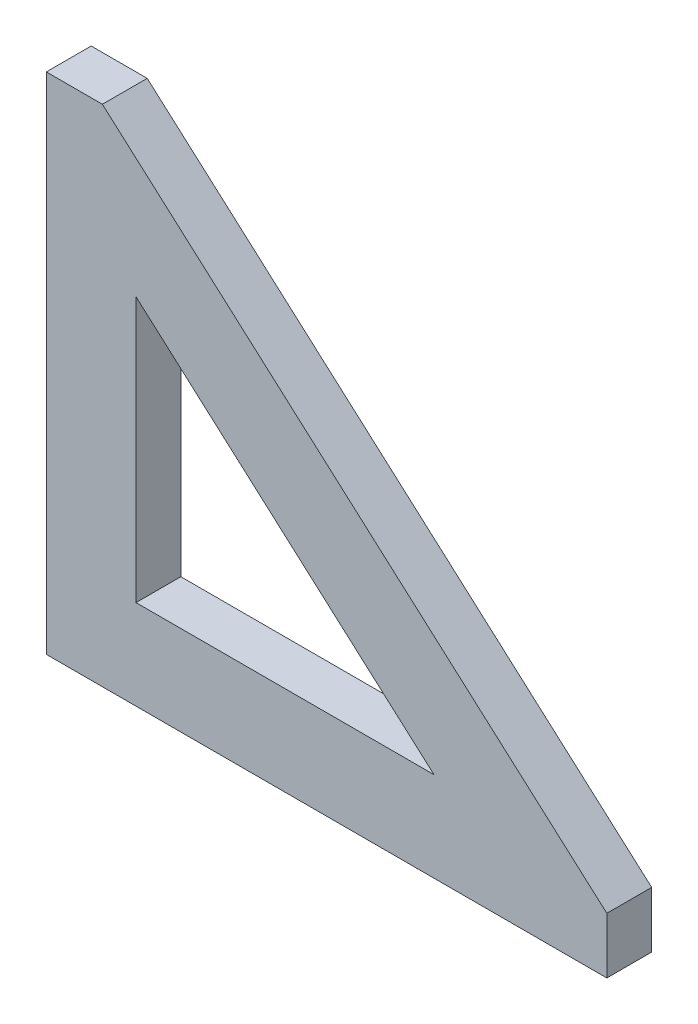
SolidWorks part; units mm, degrees
material "1060 合金"
ref_plane "前视基准面" through (0, 0, 0) normal (0, 0, 1) x (1, 0, 0)
ref_plane "上视基准面" through (0, 0, 0) normal (0, 1, 0) x (1, 0, 0)
ref_plane "右视基准面" through (0, 0, 0) normal (1, 0, 0) x (0, 0, -1)
sketch "草图1" plane through (0, 0, 0) normal (0, 0, 1) x (1, 0, 0)
  line L0 (0, 0) -> (100, 0)
  line L1 (0, 90) -> (10, 90)
  line L2 (0, 90) -> (0, 0)
  line L3 (10, 90) -> (100, 10)
  line L4 (100, 10) -> (100, 0)
  line L5 (16, 63.2594) -> (16, 63.2594)
  line L6 (16, 63.2594) -> (69.1668, 16)
  line L7 (69.1668, 16) -> (69.1668, 16)
  line L8 (16, 16) -> (69.1668, 16)
  line L9 (16, 63.2594) -> (16, 16)
  dimension "D1" = 100
  dimension "D2" = 90
  dimension "D3" = 10
  dimension "D4" = 10
  dimension "D5" = 16
extrude "凸台-拉伸1" add sketch "草图1" along normal mid plane 8
